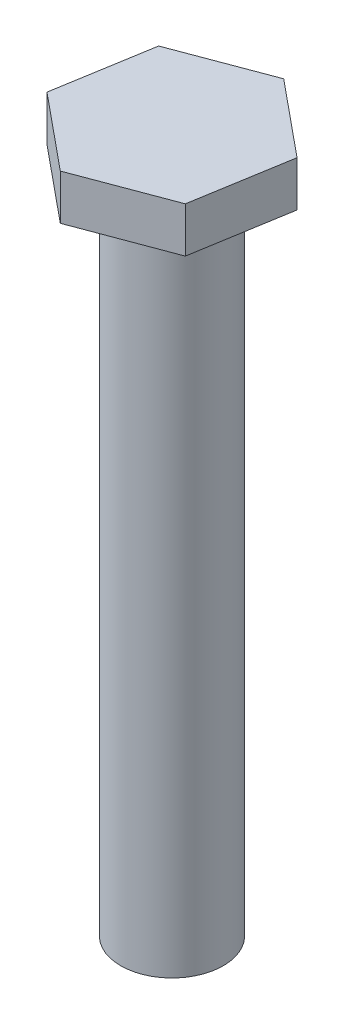
SolidWorks part; units mm, degrees
ref_plane "Front Plane" through (0, 0, 0) normal (0, 0, 1) x (1, 0, 0)
ref_plane "Top Plane" through (0, 0, 0) normal (0, 1, 0) x (1, 0, 0)
ref_plane "Right Plane" through (0, 0, 0) normal (1, 0, 0) x (0, 0, -1)
sketch "Sketch1" plane through (0, 0, 0) normal (0, 1, 0) x (1, 0, 0)
  circle A0 centre (0, 0) radius 7.9375
  dimension "D1" = 15.875
extrude "Shaft" add sketch "Sketch1" against normal blind 101.6
sketch "Sketch2" plane through (0, 0, 0) normal (0, 1, 0) x (1, 0, 0)
  line L1 (11.595, -9.5335) -> (14.0538, 5.2748)
  line L2 (14.0538, 5.2748) -> (2.4588, 14.8084)
  line L3 (2.4588, 14.8084) -> (-11.595, 9.5335)
  line L4 (-11.595, 9.5335) -> (-14.0538, -5.2748)
  line L5 (-14.0538, -5.2748) -> (-2.4588, -14.8084)
  line L6 (-2.4588, -14.8084) -> (11.595, -9.5335)
  circle A0 centre (0, 0) radius 13 construction
  dimension "D1" = 13
extrude "Head" add sketch "Sketch2" along normal blind 7
equation "\"boltLength\" = 4in"
equation "\"boltDiameter\"= 5in / 8"
equation "\"D1@Sketch1\"=\"boltDiameter\""
equation "\"D1@Shaft\" = \"boltLength\""
